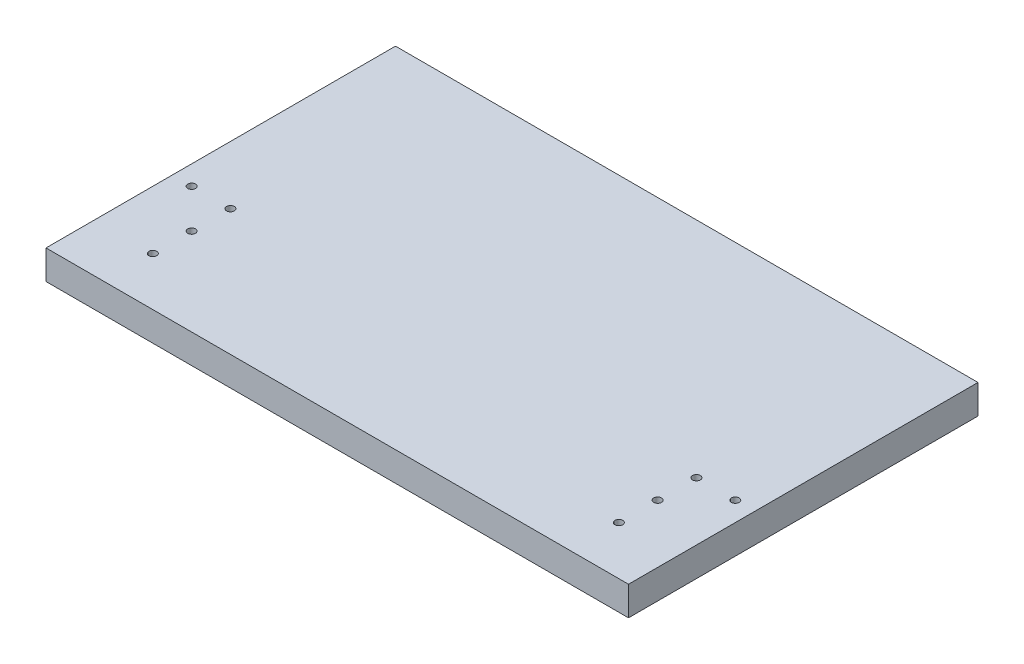
SolidWorks part; units mm, degrees
ref_plane "Alzado" through (0, 0, 0) normal (0, 0, 1) x (1, 0, 0)
ref_plane "Planta" through (0, 0, 0) normal (0, 1, 0) x (1, 0, 0)
ref_plane "Vista lateral" through (0, 0, 0) normal (1, 0, 0) x (0, 0, -1)
sketch "Croquis1" plane through (0, 0, 0) normal (0, 1, 0) x (1, 0, 0)
  line L1 (-150, -90) -> (150, -90)
  line L2 (-150, -90) -> (-150, 90)
  line L3 (-150, 90) -> (150, 90)
  line L4 (150, -90) -> (150, 90)
  line L5 (-150, -90) -> (150, 90) construction
  line L6 (-150, 90) -> (150, -90) construction
  point P0 (0, 0)
  dimension "D1" = 300
  dimension "D2" = 180
extrude "Saliente-Extruir1" add sketch "Croquis1" along normal blind 15
sketch "Croquis2" plane through (0, 15, 0) normal (0, 1, 0) x (1, 0, 0)
  line L1 (-150, -90) -> (150, -90) construction
  line L2 (-150, 90) -> (-150, -90) construction
  line L3 (150, -90) -> (150, 90) construction
  circle A0 centre (-120, -65) radius 2
  circle A1 centre (-120, -45) radius 2
  circle A2 centre (120, -65) radius 2
  circle A3 centre (120, -45) radius 2
  circle A4 centre (-140, -25) radius 2
  circle A5 centre (-120, -25) radius 2
  circle A6 centre (120, -25) radius 2
  circle A7 centre (140, -25) radius 2
  dimension "D1" = 25
  dimension "D2" = 0
  dimension "D3" = 25
  dimension "D4" = 0
  dimension "D7" = 10
  dimension "D8" = 20
  dimension "D9" = 30
  dimension "D10" = 10
  dimension "D5" = 30
  dimension "D6" = 30
  dimension "D11" = 65
  dimension "D12" = 0
  dimension "D13" = 65
  dimension "D14" = 0
  dimension "D15" = 45
  dimension "D16" = 45
extrude "Cortar-Extruir1" cut sketch "Croquis2" against normal blind 10
sketch "Croquis3" plane through (0, 0, 0) normal (0, -1, 0) x (1, 0, 0)
  line L0 (150, -90) -> (-150, -90) construction
  line L1 (-150, -90) -> (-150, 90) construction
  circle A0 centre (-140, -65) radius 2
  dimension "D1" = 25
  dimension "D2" = 10
extrude "Cortar-Extruir2" cut sketch "Croquis3" against normal blind 10
